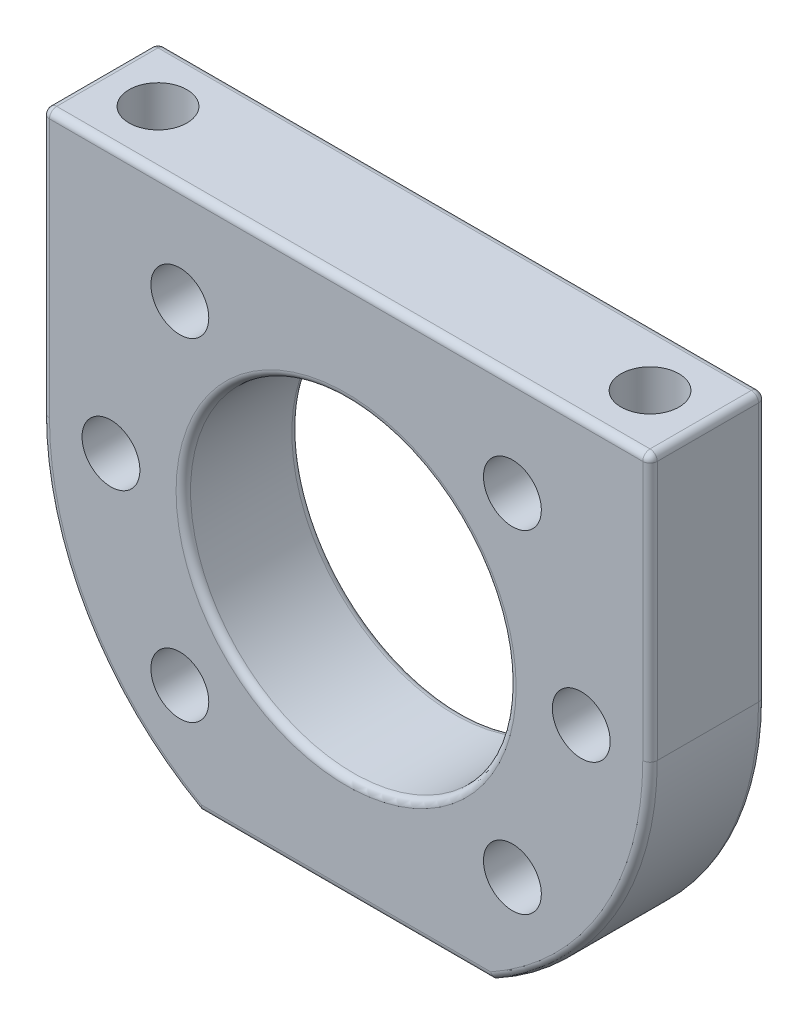
SolidWorks part; units mm, degrees
ref_plane "Front Plane" through (0, 0, 0) normal (0, 0, 1) x (1, 0, 0)
ref_plane "Top Plane" through (0, 0, 0) normal (0, 1, 0) x (1, 0, 0)
ref_plane "Right Plane" through (0, 0, 0) normal (1, 0, 0) x (0, 0, -1)
sketch "Sketch1" plane through (0, 0, 0) normal (0, 0, 1) x (1, 0, 0)
  line L0 (21, 0) -> (21, 18.4)
  line L3 (-10.1213, -18.4) -> (10.1213, -18.4)
  line L4 (-21, 0) -> (-21, 18.4)
  line L5 (-21, 18.4) -> (21, 18.4)
  arc A0 (10.1213, -18.4) -> (21, 0) centre (0, 0) ccw
  arc A1 (-21, 0) -> (-10.1213, -18.4) centre (0, 0) ccw
  dimension "D1" = 21
  dimension "D4" = 21
  dimension "D2" = 21
  dimension "D3" = 18.4
  dimension "D5" = 36.8
extrude "Boss-Extrude1" add sketch "Sketch1" along normal mid plane 8
sketch "Sketch2" plane through (0, 0, 4) normal (0, 0, 1) x (1, 0, 0)
  circle A0 centre (0, 0) radius 11.25
  dimension "D1" = 22.5
extrude "Cut-Extrude1" cut sketch "Sketch2" against normal through all
sketch "Sketch3" plane through (0, 0, 4) normal (0, 0, 1) x (1, 0, 0)
  line L0 (0, 21) -> (0, -21) construction
  line L1 (0, 0) -> (-19.8057, 19.8057) construction
  line L2 (0, 0) -> (19.0248, 19.0248) construction
  circle A0 centre (-16.25, 0) radius 2
  circle A1 centre (16.25, 0) radius 2
  circle A2 centre (0, 0) radius 16.25 construction
  circle A3 centre (-11.4905, 11.4905) radius 2
  circle A5 centre (11.4905, 11.4905) radius 2
  circle A6 centre (11.4905, -11.4905) radius 2
  circle A8 centre (-11.4905, -11.4905) radius 2
  dimension "D3" = 32.5
  dimension "D4" = 4
  dimension "D5" = 4
  dimension "D6" = 4
  dimension "D7" = 4
  dimension "D8" = 4
  dimension "D9" = 4
  dimension "D1" = 45
  dimension "D2" = 45
extrude "Cut-Extrude2" cut sketch "Sketch3" against normal blind 8
sketch "Sketch6" plane through (-3.375, 18.4, 0) normal (0, -1, 0) x (0, 0, -1)
  line L0 (0, -996.625) -> (0, 49003.375) construction
  circle A0 centre (0, -13.625) radius 2
  circle A1 centre (0, 20.375) radius 2
  dimension "D1" = 17
  dimension "D2" = 17
  dimension "D3" = 4
  dimension "D4" = 4
extrude "Cut-Extrude3" cut sketch "Sketch6" along normal blind 8
fillet "Fillet1" radius 0.5 16 edges at (0, -18.4, -4) (0, -18.4, 4) (-21, 9.2, 4) (11.25, 0, 4) (-21, 18.4, 0) (0, 18.4, -4) (0, 18.4, 4) (11.25, 0, -4) (-21, 9.2, -4) (-18.0769, -10.6877, -4) (-18.0769, -10.6877, 4) (18.0769, -10.6877, -4) (21, 18.4, 0) (21, 9.2, -4) (18.0769, -10.6877, 4) (21, 9.2, 4)
equation "\"D6@Sketch3\"=\"D5@Sketch3\""
equation "\"D9@Sketch3\"=\"D5@Sketch3\""
equation "\"D8@Sketch3\"=\"D5@Sketch3\""
equation "\"D7@Sketch3\"=\"D5@Sketch3\""
equation "\"D4@Sketch3\"=\"D5@Sketch3\""
equation "\"D1@Sketch6\"=34/2"
equation "\"D4@Sketch6\"=\"D3@Sketch6\""
equation "\"D3@Sketch1\"=\"D5@Sketch1\"/2"
equation "\"D2@Sketch6\"=\"D1@Sketch6\""
